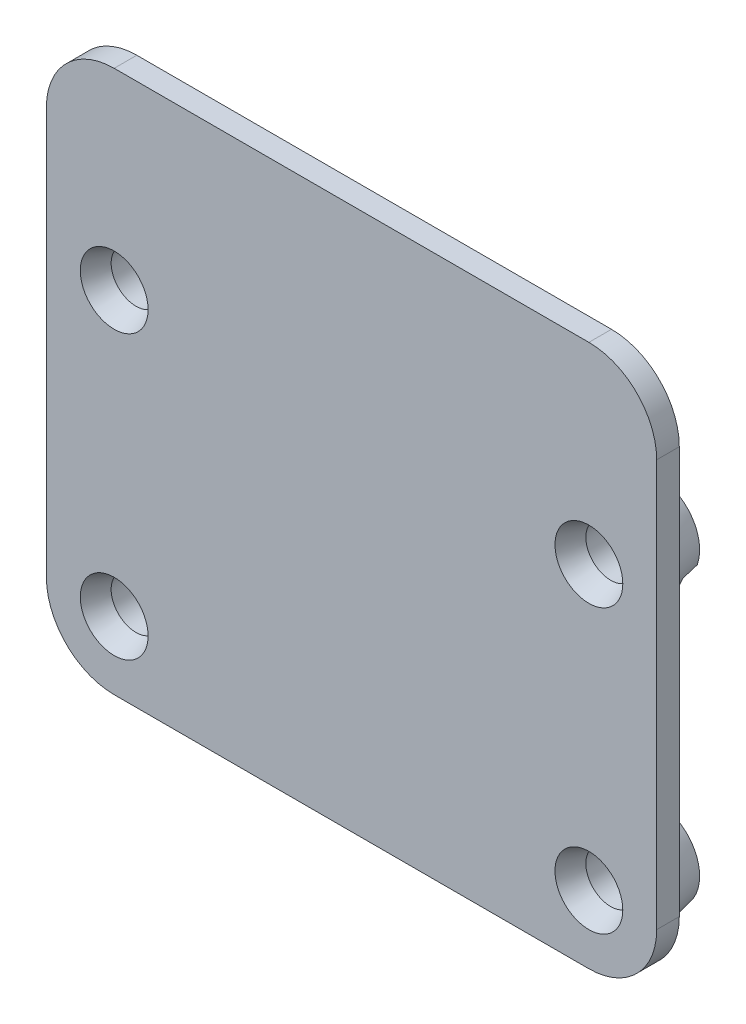
SolidWorks part; units mm, degrees
ref_plane "Front Plane" through (0, 0, 0) normal (0, 0, 1) x (1, 0, 0)
ref_plane "Top Plane" through (0, 0, 0) normal (0, 1, 0) x (1, 0, 0)
ref_plane "Right Plane" through (0, 0, 0) normal (1, 0, 0) x (0, 0, -1)
sketch "Sketch1" plane through (0, 0, 0) normal (0, 0, 1) x (1, 0, 0)
  line L0 (0, 13.48) -> (0, -10.52) construction
  line L1 (10.5, 13.48) -> (-10.5, 13.48)
  line L2 (13.5, 10.48) -> (13.5, -7.52)
  line L3 (10.5, -10.52) -> (-10.5, -10.52)
  line L4 (-13.5, 10.48) -> (-13.5, -7.52)
  arc A0 (-10.5, -10.52) -> (-13.5, -7.52) centre (-10.5, -7.52) cw
  arc A1 (-10.5, 13.48) -> (-13.5, 10.48) centre (-10.5, 10.48) ccw
  arc A2 (10.5, 13.48) -> (13.5, 10.48) centre (10.5, 10.48) cw
  arc A3 (13.5, -7.52) -> (10.5, -10.52) centre (10.5, -7.52) cw
  point P4 (10.5, 4.98)
  point P5 (10.5, -7.52)
  point P7 (-10.5, -7.52)
  point P9 (-10.5, 4.98)
  point P17 (-13.5, -10.52)
  point P20 (-13.5, 13.48)
  dimension "D4" = 3
  dimension "D1" = 3
  dimension "D2" = 3
  dimension "D3" = 24
extrude "Boss-Extrude1" add sketch "Sketch1" along normal blind 1
sketch "Sketch4" plane through (0, 0, 0) normal (0, 0, -1) x (-1, 0, 0)
  circle A0 centre (-10.5, 4.98) radius 2.3
  circle A1 centre (10.5, 4.98) radius 2.3
  circle A2 centre (10.5, -7.52) radius 2.3
  circle A3 centre (-10.5, -7.52) radius 2.3
  dimension "D1" = 4.6
extrude "Boss-Extrude2" add sketch "Sketch4" along normal blind 2
hole_wizard "M2 Clearance Hole1" positions "Sketch2" profile "Sketch3" hole size "M2" standard "ISO" end condition through all
sketch "Sketch2" plane through (0, 0, 1) normal (0, 0, 1) x (1, 0, 0)
  point P0 (10.5, 4.98)
  point P2 (10.5, -7.52)
  point P4 (-10.5, -7.52)
  point P6 (-10.5, 4.98)
sketch "Sketch3" plane through (10.5, 4.98, 1) normal (1, 0, 0) x (0, -1, 0)
  line L0 (0, 0) -> (0, 3)
  line L1 (0, 3) -> (1.1, 3)
  line L2 (1.1, 3) -> (1.1, 0.9657)
  line L3 (1.1, 0.9657) -> (1.5, 0)
  line L5 (1.5, 0) -> (0, 0)
  line L6 (-1.1, 0.9657) -> (-1.5, 0) construction
  line L11 (0, -6.35) -> (0, 107.95) construction
  dimension "Thru Hole Dia." = 2.2
  dimension "Thru Hole Depth" = 3
  dimension "Near C'Sink Dia." = 3
  dimension "Near C'Sink Angle" = 45
chamfer "Chamfer1" distance 2 distance2 0.4 4 edges at (-12.8, -7.52, -2) (-12.8, 4.98, -2) (8.2, 4.98, -2) (8.2, -7.52, -2) first distance on face at (-12.8, -7.52, -2) first distance on face at (-12.8, 4.98, -2) first distance on face at (8.2, 4.98, -2) first distance on face at (8.2, -7.52, -2)
sketch "Sketch5" plane through (0, 0, -2) normal (0, 0, -1) x (-1, 0, 0)
  line L0 (8.7085, 6.4224) -> (10.5, 4.98)
  line L1 (10.5, 4.98) -> (9.192, 3.0882)
  line L2 (10.3585, -9.8156) -> (10.5, -7.52)
  line L3 (10.5, -7.52) -> (8.2574, -8.0304)
  line L4 (-12.671, 4.2206) -> (-10.5, 4.98)
  line L5 (-10.5, 4.98) -> (-10.7577, 2.6945)
  line L6 (-9.8628, -5.31) -> (-10.5133, -7.566)
  line L7 (-10.5133, -7.566) -> (-8.2, -7.52)
  arc A0 (8.7085, 6.4224) -> (9.192, 3.0882) centre (10.5, 4.98) ccw
  circle A1 centre (10.5, 4.98) radius 2.3 construction
  arc A2 (8.2574, -8.0304) -> (10.3585, -9.8156) centre (10.5, -7.52) ccw
  circle A3 centre (10.5, -7.52) radius 2.3 construction
  arc A4 (-9.8628, -5.31) -> (-8.2, -7.52) centre (-10.5, -7.52) cw
  circle A5 centre (-10.5, -7.52) radius 2.3 construction
  arc A6 (-12.671, 4.2206) -> (-10.7577, 2.6945) centre (-10.5, 4.98) ccw
  circle A7 centre (-10.5, 4.98) radius 2.3 construction
extrude "Cut-Extrude2" cut sketch "Sketch5" against normal blind 0.8
